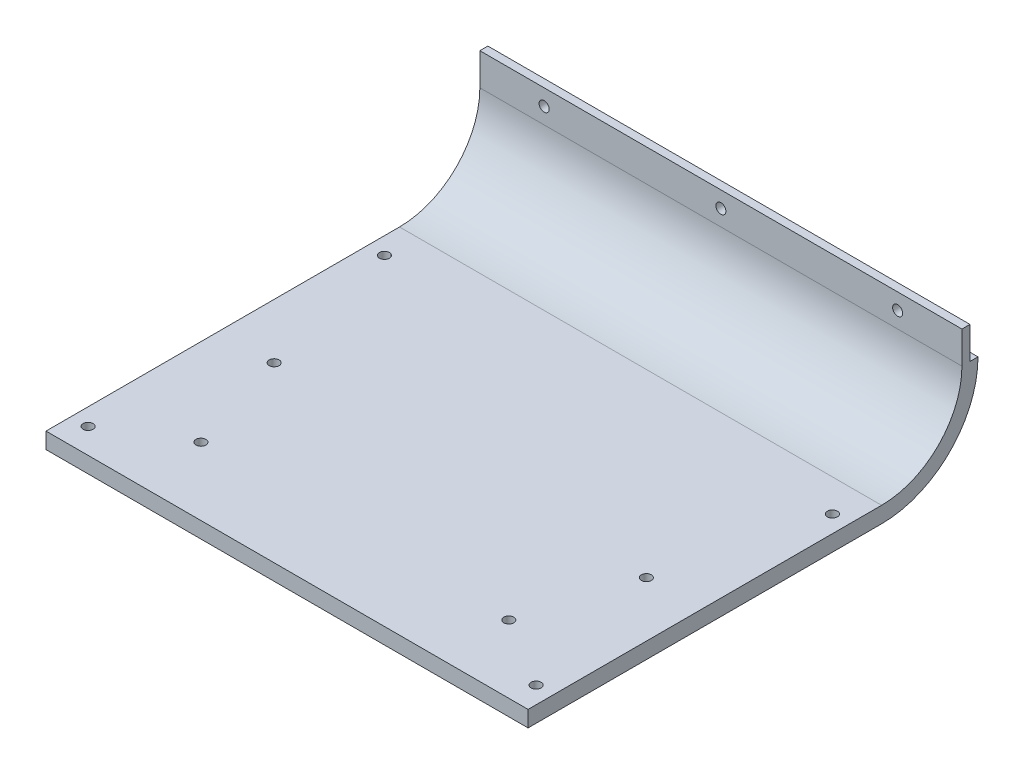
SolidWorks part; units mm, degrees
material "6061-T6 Aluminum"
ref_plane "Front Plane" through (0, 0, 0) normal (0, 0, 1) x (1, 0, 0)
ref_plane "Top Plane" through (0, 0, 0) normal (0, 1, 0) x (1, 0, 0)
ref_plane "Right Plane" through (0, 0, 0) normal (1, 0, 0) x (0, 0, -1)
sketch "Sketch1" plane through (0, 0, 0) normal (1, 0, 0) x (0, 0, -1)
  line L0 (-139.7, 0) -> (139.7, 0)
  line L5 (139.7, 0) -> (139.7, 12.7) construction
  line L7 (-139.7, 12.7) -> (139.7, 12.7)
  line L9 (-139.7, 0) -> (-139.7, 12.7)
  line L12 (139.7, 0) -> (139.7, 152.4) construction
  line L13 (0.6365, 139.0796) -> (-139.7417, 139.9778) construction
  line L14 (-12.6991, 151.8652) -> (-139.6605, 152.6775) construction
  line L15 (203.2, 76.2) -> (215.9, 76.2)
  arc A2 (139.7, 0) -> (-12.6991, 151.8652) centre (139.7, 152.4) ccw construction
  arc A3 (139.7, 12.7) -> (0.6365, 139.0796) centre (139.7, 152.4) ccw construction
  circle A5 centre (139.7, 76.2) radius 76.2 construction
  arc A6 (215.9, 76.2) -> (139.7, 0) centre (139.7, 76.2) cw
  circle A7 centre (139.7, 76.2) radius 63.5 construction
  arc A8 (203.2, 76.2) -> (139.7, 12.7) centre (139.7, 76.2) cw
  point P3 (0, 0)
  dimension "D1" = 152.4
  dimension "D2" = 12.7
  dimension "D4" = 127
  dimension "D6" = 12.7
  dimension "D3" = 12.7
  dimension "D5" = 12.7
  dimension "D7" = 355.6
extrude "Boss-Extrude1" add sketch "Sketch1" along normal blind 190.5 and the other way blind 190.5
sketch "Sketch2" plane through (0, 76.2, 0) normal (0, 1, 0) x (1, 0, 0)
  line L0 (-190.5, 215.9) -> (-190.5, 203.2) construction
  line L1 (-190.5, 209.55) -> (190.5, 209.55)
  line L2 (-190.5, 209.55) -> (-190.5, 203.2)
  line L3 (-190.5, 203.2) -> (190.5, 203.2)
  line L4 (190.5, 209.55) -> (190.5, 203.2)
extrude "Boss-Extrude2" add sketch "Sketch2" along normal blind 25.4
sketch "Sketch3" plane through (0, 0, -209.55) normal (0, 0, -1) x (-1, 0, 0)
  line L0 (-190.5, 88.9) -> (190.5, 88.9) construction
  line L1 (-190.5, 101.6) -> (-190.5, 76.2) construction
  line L2 (190.5, 101.6) -> (190.5, 76.2) construction
  line L3 (-139.7, 101.6) -> (-139.7, 76.2) construction
  line L4 (-190.5, 101.6) -> (190.5, 101.6) construction
  line L5 (-190.5, 76.2) -> (190.5, 76.2) construction
  line L6 (0, 101.6) -> (0, 76.2) construction
  line L7 (190.5, 76.2) -> (-190.5, 76.2) construction
  line L8 (139.7, 101.6) -> (139.7, 76.2) construction
  circle A0 centre (-139.7, 88.9) radius 3.9687
  circle A1 centre (139.7, 88.9) radius 3.9687
  circle A2 centre (0, 88.9) radius 3.9687
  dimension "D3" = 7.9375
  dimension "D1" = 139.7
  dimension "D2" = 139.7
extrude "Cut-Extrude1" cut sketch "Sketch3" against normal blind 25.4
sketch "Sketch4" plane through (0, 12.7, 0) normal (0, 1, 0) x (1, 0, 0)
  line L0 (0, -139.7) -> (0, -119.888) construction
  line L1 (-190.5, -139.7) -> (190.5, -139.7) construction
  line L2 (0, -119.888) -> (0, 0) construction
  line L3 (0, 0) -> (0, 114.3) construction
  line L4 (-147.066, -2.794) -> (147.066, -2.794) construction
  line L5 (-190.5, 139.7) -> (-190.5, -139.7) construction
  line L6 (-177.038, 114.3) -> (177.038, 114.3) construction
  line L7 (-121.666, -86.106) -> (121.666, -86.106) construction
  line L8 (-177.038, -119.888) -> (177.038, -119.888) construction
  line L10 (190.5, 139.7) -> (190.5, -139.7) construction
  circle A0 centre (177.038, -119.888) radius 3.937
  circle A2 centre (177.038, 114.3) radius 3.937
  circle A3 centre (-177.038, -119.888) radius 3.937
  circle A5 centre (-177.038, 114.3) radius 3.937
  circle A6 centre (147.066, -2.794) radius 3.937
  circle A7 centre (-147.066, -2.794) radius 3.937
  circle A8 centre (121.666, -86.106) radius 3.937
  circle A9 centre (-121.666, -86.106) radius 3.937
  point P12 (0, 114.3)
  point P15 (0, 0)
  point P19 (0, -119.888)
  dimension "D3" = 7.874
  dimension "D4" = 254
  dimension "D7" = 7.874
  dimension "D12" = 7.874
  dimension "D1" = 19.812
  dimension "D2" = 13.462
  dimension "D5" = 43.434
  dimension "D6" = 136.906
  dimension "D8" = 43.434
  dimension "D9" = 68.834
  dimension "D10" = 68.834
  dimension "D11" = 53.594
extrude "Cut-Extrude2" cut sketch "Sketch4" against normal through all
